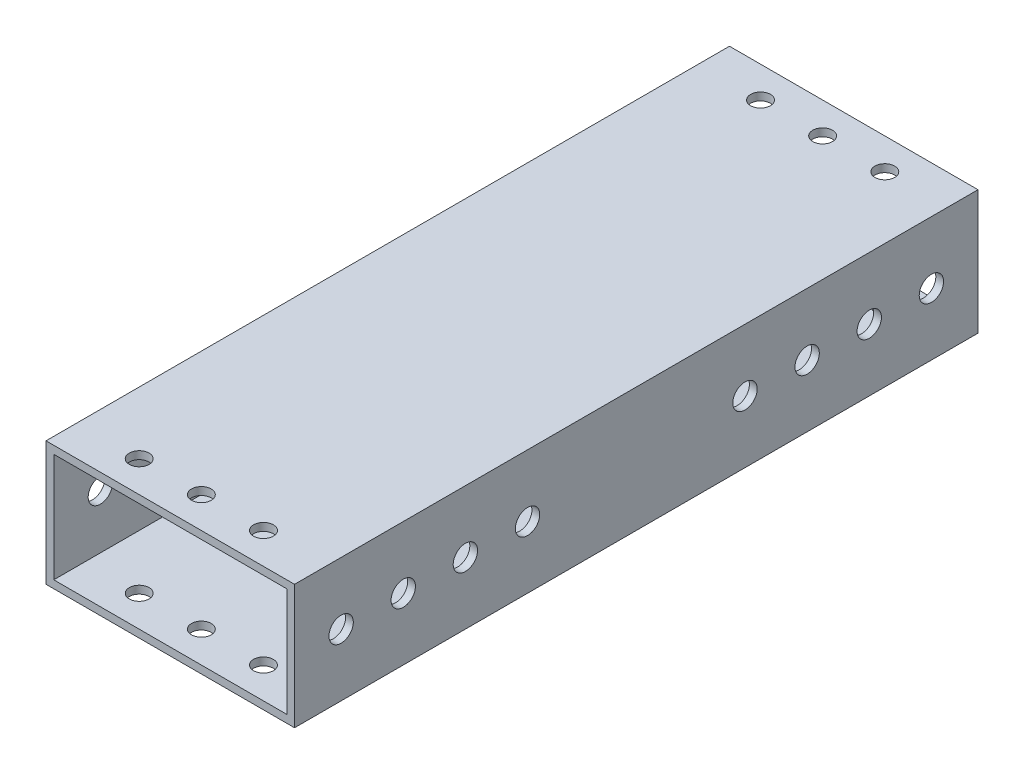
SolidWorks part; units mm, degrees
material "6061-T6 (SS)"
ref_plane "Front Plane" through (0, 0, 0) normal (0, 0, 1) x (1, 0, 0)
ref_plane "Top Plane" through (0, 0, 0) normal (0, 1, 0) x (1, 0, 0)
ref_plane "Right Plane" through (0, 0, 0) normal (1, 0, 0) x (0, 0, -1)
sketch "Sketch1" plane through (0, 0, 0) normal (0, 0, 1) x (1, 0, 0)
  line L0 (-23.8125, 11.1125) -> (23.8125, 11.1125)
  line L1 (-25.4, -12.7) -> (25.4, -12.7)
  line L2 (-25.4, -12.7) -> (-25.4, 12.7)
  line L3 (-25.4, 12.7) -> (25.4, 12.7)
  line L4 (25.4, -12.7) -> (25.4, 12.7)
  line L5 (-25.4, -12.7) -> (25.4, 12.7) construction
  line L6 (-25.4, 12.7) -> (25.4, -12.7) construction
  line L7 (23.8125, -11.1125) -> (23.8125, 11.1125)
  line L8 (-23.8125, -11.1125) -> (23.8125, -11.1125)
  line L9 (-23.8125, -11.1125) -> (-23.8125, 11.1125)
  point P0 (0, 0)
  dimension "D1" = 50.8
  dimension "D2" = 25.4
  dimension "D3" = 1.5875
extrude "Boss-Extrude1" add sketch "Sketch1" along normal mid plane 139.7
sketch "Sketch2" plane through (0, 12.7, 0) normal (0, 1, 0) x (1, 0, 0)
  line L0 (25.4, 69.85) -> (-25.4, 69.85) construction
  line L1 (25.4, 0) -> (-25.4, 0) construction
  line L2 (25.4, -69.85) -> (25.4, 69.85) construction
  line L3 (-25.4, -69.85) -> (-25.4, 69.85) construction
  circle A0 centre (-12.7, 63.5) radius 2.0193
  circle A1 centre (0, 63.5) radius 2.0193
  circle A2 centre (12.7, 63.5) radius 2.0193
  circle A3 centre (12.7, -63.5) radius 2.0193
  circle A4 centre (0, -63.5) radius 2.0193
  circle A5 centre (-12.7, -63.5) radius 2.0193
  dimension "D1" = 4.0386
  dimension "D2" = 12.7
  dimension "D3" = 12.7
  dimension "D4" = 6.35
extrude "Cut-Extrude1" cut sketch "Sketch2" against normal through all
sketch "Sketch3" plane through (25.4, 0, 0) normal (1, 0, 0) x (0, 0, -1)
  line L0 (0, 12.7) -> (0, -12.7) construction
  line L1 (-69.85, 12.7) -> (69.85, 12.7) construction
  line L2 (-69.85, -12.7) -> (69.85, -12.7) construction
  line L3 (-69.85, -12.7) -> (-69.85, 12.7) construction
  circle A0 centre (-60.325, 0) radius 2.4892
  circle A1 centre (60.325, 0) radius 2.4892
  circle A2 centre (-47.625, 0) radius 2.4892
  circle A3 centre (-34.925, 0) radius 2.4892
  circle A4 centre (34.925, 0) radius 2.4892
  circle A5 centre (47.625, 0) radius 2.4892
  circle A6 centre (-22.225, 0) radius 2.4892
  circle A7 centre (22.225, 0) radius 2.4892
  dimension "D1" = 12.7
  dimension "D3" = 4.9784
  dimension "D2" = 9.525
  dimension "D4" = 12.7
  dimension "D5" = 12.7
extrude "Cut-Extrude2" cut sketch "Sketch3" against normal through all
